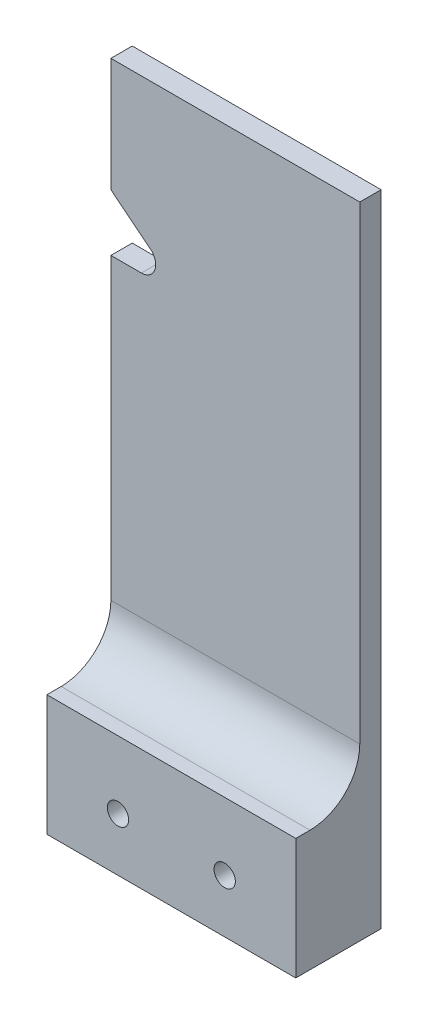
SolidWorks part; units mm, degrees
ref_plane "前视基准面" through (0, 0, 0) normal (0, 0, 1) x (1, 0, 0)
ref_plane "上视基准面" through (0, 0, 0) normal (0, 1, 0) x (1, 0, 0)
ref_plane "右视基准面" through (0, 0, 0) normal (1, 0, 0) x (0, 0, -1)
other "Configuration Table"
sketch "草图1" plane through (0, 0, 0) normal (0, 0, 1) x (1, 0, 0)
  line L1 (-17.5, -45) -> (17.5, -45)
  line L2 (-17.5, -45) -> (-17.5, 45)
  line L3 (-17.5, 45) -> (17.5, 45)
  line L4 (17.5, -45) -> (17.5, 45)
  line L5 (-17.5, -45) -> (17.5, 45) construction
  line L6 (-17.5, 45) -> (17.5, -45) construction
  point P0 (0, 0)
  dimension "D1" = 90
  dimension "D2" = 35
extrude "凸台-拉伸1" add sketch "草图1" along normal blind 3
sketch "草图2" plane through (0, 0, 3) normal (0, 0, 1) x (1, 0, 0)
  line L0 (17.5, -45) -> (17.5, 45) construction
  line L1 (-17.5, -45) -> (17.5, -45)
  line L2 (-17.5, -45) -> (-17.5, -28)
  line L3 (-17.5, -28) -> (17.5, -28)
  line L4 (17.5, -45) -> (17.5, -28)
  dimension "D1" = 17
extrude "凸台-拉伸2" add sketch "草图2" along normal blind 9
fillet "圆角1" radius 7 1 edges at (0, -28, 3)
sketch "草图3" plane through (0, 0, 12) normal (0, 0, 1) x (1, 0, 0)
  line L0 (-17.5, -28) -> (-17.5, -45) construction
  line L1 (17.5, -45) -> (17.5, -28) construction
  line L2 (-17.5, -45) -> (17.5, -45) construction
  circle A0 centre (-7.5, -37.5) radius 1.5
  circle A1 centre (7.5, -37.5) radius 1.5
  dimension "D1" = 3
  dimension "D2" = 3
  dimension "D3" = 10
  dimension "D4" = 10
  dimension "D5" = 7.5
  dimension "D6" = 7.5
extrude "切除-拉伸3" cut sketch "草图3" against normal through all
sketch "草图4" plane through (0, 0, 0) normal (0, 0, -1) x (-1, 0, 0)
  line L5 (17.5, 21) -> (7.5, 21)
  line L6 (17.5, 45) -> (17.5, -45) construction
  line L7 (7.5, 21) -> (17.5, 29)
  line L8 (17.5, 29) -> (17.5, 21)
  line L9 (-17.5, 45) -> (17.5, 45) construction
  dimension "D4" = 16
  dimension "D5" = 8
  dimension "D6" = 10
extrude "切除-拉伸4" cut sketch "草图4" against normal through all
fillet "圆角2" radius 2 1 edges at (-7.5, 21, 1.5)
